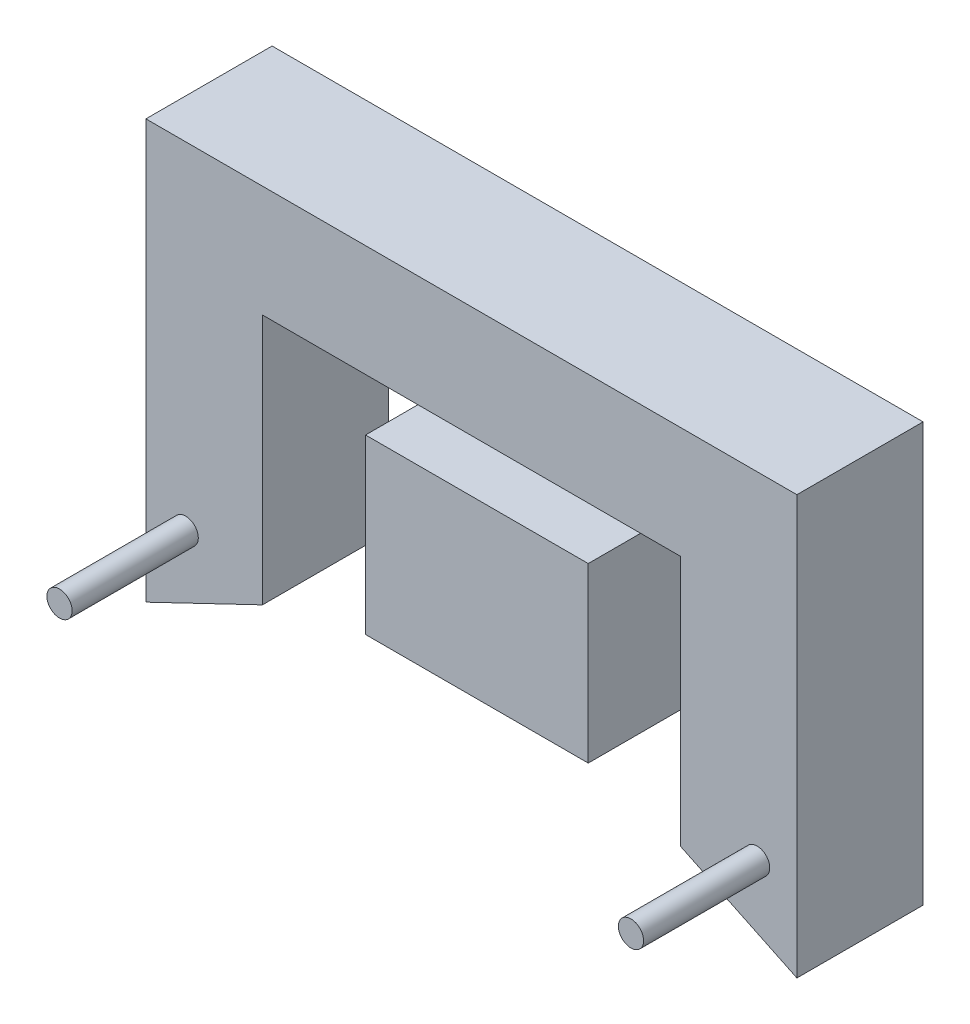
SolidWorks part; units mm, degrees
ref_plane "Front Plane" through (0, 0, 0) normal (0, 0, 1) x (1, 0, 0)
ref_plane "Top Plane" through (0, 0, 0) normal (0, 1, 0) x (1, 0, 0)
ref_plane "Right Plane" through (0, 0, 0) normal (1, 0, 0) x (0, 0, -1)
sketch "Sketch2" plane through (0, 0, 0) normal (0, 0, 1) x (1, 0, 0)
  line L0 (-185.6926, 7.7337) -> (-167.2195, 7.7337)
  line L1 (-185.6926, -5.2284) -> (-185.6926, 61.1183)
  line L2 (-185.6926, 61.1183) -> (-82.5011, 61.1183)
  line L3 (-167.2195, 3.6345) -> (-167.2195, 43.4324)
  line L4 (-167.2195, 43.4324) -> (-100.9743, 43.4324)
  line L5 (-100.9743, 3.6345) -> (-100.9743, 43.4324)
  line L6 (-82.5011, -5.2284) -> (-82.5011, 61.1183)
  line L7 (-82.5011, 7.7337) -> (-100.9743, 7.7337)
  line L8 (-150.8783, 35.1272) -> (-115.5797, 35.1272)
  line L9 (-150.8783, 35.1272) -> (-150.8783, 7.7337)
  line L10 (-150.8783, 7.7337) -> (-115.5797, 7.7337)
  line L11 (-115.5797, 35.1272) -> (-115.5797, 7.7337)
  line L12 (-185.6926, -5.2284) -> (-167.2195, 3.6345)
  line L13 (-82.5011, -5.2284) -> (-100.9743, 3.6345)
  circle A0 centre (-179.3898, 7.7337) radius 2
  circle A1 centre (-88.804, 7.7337) radius 2
  point P10 (-134.0969, 43.4324)
extrude "Boss-Extrude10" add sketch "Sketch2" along normal blind 20 contours A0 | A1 | L3 L4 L5 L13 L6 L2 L1 L12
sketch "Sketch7" plane through (0, 0, 20) normal (0, 0, 1) x (1, 0, 0)
  circle A0 centre (-179.3898, 7.7337) radius 2
extrude "Boss-Extrude11" add sketch "Sketch7" along normal blind 20 separate body
sketch "Sketch8" plane through (0, 0, 20) normal (0, 0, 1) x (1, 0, 0)
  circle A0 centre (-88.804, 7.7337) radius 2
extrude "Boss-Extrude12" add sketch "Sketch8" along normal blind 20 separate body
extrude "Boss-Extrude13" add sketch "Sketch2<14>" along normal blind 20 separate body contours L8 L11 L10 L9
sketch "Sketch2<14>" plane through (0, 0, 0) normal (0, 0, 1) x (1, 0, 0) same geometry as "Sketch2"
